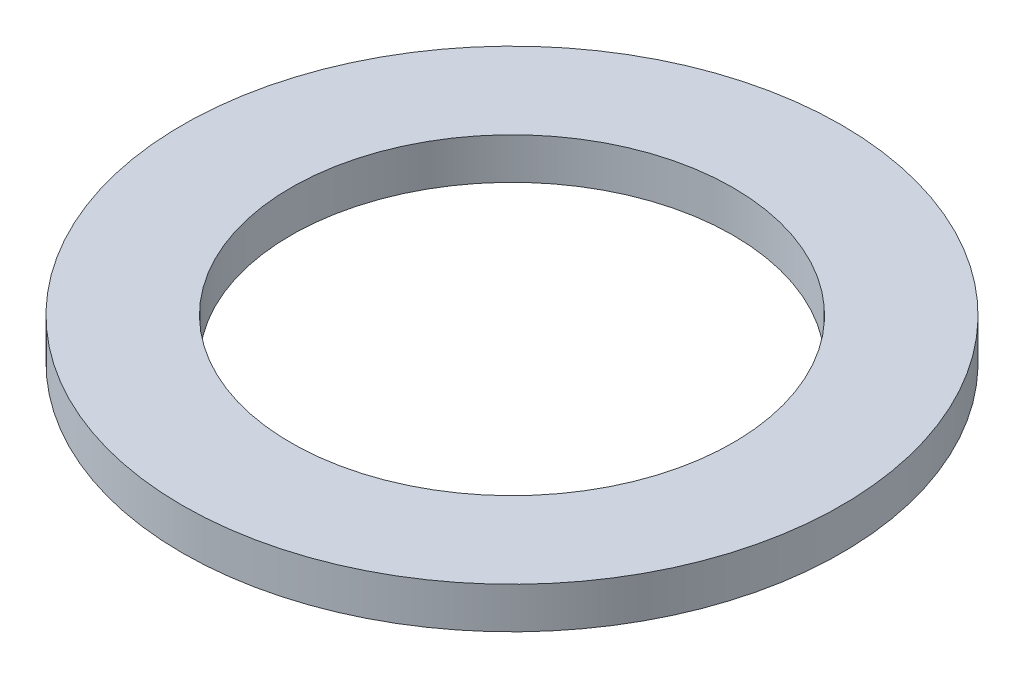
SolidWorks part; units mm, degrees
material "6061 Alloy"
ref_plane "Front Plane" through (0, 0, 0) normal (0, 0, 1) x (1, 0, 0)
ref_plane "Top Plane" through (0, 0, 0) normal (0, 1, 0) x (1, 0, 0)
ref_plane "Right Plane" through (0, 0, 0) normal (1, 0, 0) x (0, 0, -1)
sketch "Sketch1" plane through (0, 0, 0) normal (0, 1, 0) x (1, 0, 0)
  circle A0 centre (0, 0) radius 51.1048
  circle A1 centre (0, 0) radius 76.2
  dimension "D1" = 102.2096
  dimension "D2" = 152.4
extrude "Boss-Extrude1" add sketch "Sketch1" along normal blind 9.525
equation "\"Ring Thickness\"= 0.375"
equation "\"Outer Diameter\"= 6"
equation "\"Inner Diameter\"= 4.024"
equation "\"D1@Sketch1\"=\"Inner Diameter\""
equation "\"D2@Sketch1\"=\"Outer Diameter\""
equation "\"D1@Boss-Extrude1\"=\"Ring Thickness\""
